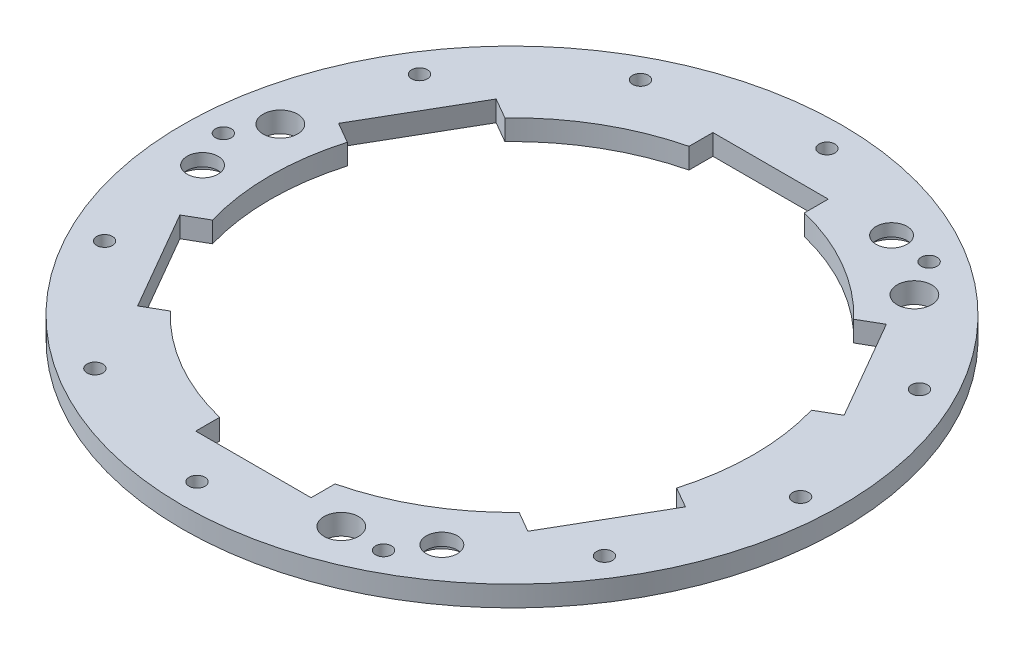
SolidWorks part; units mm, degrees
material "6061 Alloy"
ref_plane "Front Plane" through (0, 0, 0) normal (0, 0, 1) x (1, 0, 0)
ref_plane "Top Plane" through (0, 0, 0) normal (0, 1, 0) x (1, 0, 0)
ref_plane "Right Plane" through (0, 0, 0) normal (1, 0, 0) x (0, 0, -1)
sketch "Sketch1" plane through (0, 0, 0) normal (0, 1, 0) x (1, 0, 0)
  line L0 (-13.335, -54.2656) -> (-13.335, -58.1814)
  line L1 (13.335, -54.2656) -> (13.335, -58.1814)
  line L2 (-13.335, -59.7901) -> (13.335, -59.7901)
  line L3 (13.335, -58.1814) -> (13.335, -59.7901)
  line L4 (-13.335, -58.1814) -> (-13.335, -59.7901)
  line L5 (0, 0) -> (-65.7887, -5.7558) construction
  line L6 (0, 0) -> (-3.0468, -69.7835) construction
  line L7 (0, 0) -> (0, -26.4169) construction
  line L9 (-65.0367, 11.4677) -> (0, 0) construction
  circle A0 centre (0, 0) radius 55.88
  circle A1 centre (0, 0) radius 76.2
  circle A2 centre (0, 0) radius 59.69
  circle A3 centre (-3.0468, -69.7835) radius 1.8288
  circle A4 centre (-65.7887, -5.7558) radius 3.589
  circle A5 centre (-65.0367, 11.4677) radius 3.9903
  point P24 (0, 0)
  point P29 (0, 0)
  dimension "D1" = 111.76
  dimension "D2" = 152.4
  dimension "D8" = 3.6576
  dimension "D11" = 7.178
  dimension "D12" = 7.9807
  dimension "D4" = 13.335
  dimension "D5" = 13.335
  dimension "D7" = 69.85
  dimension "D6" = 5.5245
  dimension "D9" = 66.04
  dimension "D10" = 82.5
  dimension "D15" = 15
  dimension "D13" = 2.5
  dimension "D3" = 3.81
extrude "Boss-Extrude1" add sketch "Sketch1" along normal blind 4.7625 contours L1 A2 L0 A0 | A1 A2 A0 region at (-15.0127, 0, 56.2235) region at (-74.0447, 0, 0)
pattern_circular "CirPattern1" count 6 over 360 about axis through (0, 4.7625, 0) along (0, 1, 0) of face at (-13.335, 2.3813, 57.0278) of face at (13.335, 2.3813, 57.0278) of face at (0, 2.3813, 59.7901)
pattern_circular "CirPattern7" count 12 over 360 about axis through (0, 4.7625, 0) along (0, 1, 0) of face at (-3.0468, 4.7625, 71.6123)
sketch "Sketch4" plane through (0, 0, 0) normal (0, -1, 0) x (1, 0, 0)
  line L0 (0, 0) -> (-65.7887, 5.7558) construction
  line L1 (0, 0) -> (0, -39.7137) construction
  circle A0 centre (-65.7887, 5.7558) radius 5.588
  circle A2 centre (-65.7887, 5.7558) radius 3.589 construction
  circle A3 centre (-65.7887, 5.7558) radius 3.589
  point P12 (0, 0)
  dimension "D2" = 11.176
extrude "Cut-Extrude1" cut sketch "Sketch4" against normal blind 1.905 contours A0 region at (-71.2186, 0, 5.7558)
pattern_circular "CirPattern2" count 3 over 360 about axis through (0, 0, 0) along (0, 1, 0) of face at (-65.7887, 4.7625, 9.3448) of face at (-65.7887, 1.905, 2.1667) of face at (-65.7887, 1.905, 0.1678) of face at (-65.0367, 4.7625, -7.4774)
sketch "Sketch5" plane through (0, 4.7625, 0) normal (0, 1, 0) x (1, 0, 0)
  line L0 (0, 0) -> (-20.0894, -55.1952)
  line L1 (0, 0) -> (0, -18.6852)
  line L2 (-16.5968, -53.0258) -> (-18.2257, -57.5011) construction
  line L3 (-18.2257, -57.5011) -> (-22.9993, -55.7636) construction
  line L4 (-22.9993, -55.7636) -> (-21.3704, -51.2884) construction
  line L5 (-59.7924, -7.9638) -> (-55.1022, -7.1368)
  line L6 (-54.2201, -12.1397) -> (-58.9103, -12.9667)
  line L7 (-58.9103, -12.9667) -> (-59.7924, -7.9638)
  line L8 (-36.7931, 47.7998) -> (-33.7318, 44.1515)
  line L9 (-37.6233, 40.8862) -> (-40.6846, 44.5345)
  line L10 (-40.6846, 44.5345) -> (-36.7931, 47.7998)
  line L11 (22.9993, 55.7636) -> (21.3704, 51.2884)
  line L12 (16.5968, 53.0258) -> (18.2257, 57.5011)
  line L13 (18.2257, 57.5011) -> (22.9993, 55.7636)
  line L14 (59.7924, 7.9638) -> (55.1022, 7.1368)
  line L15 (54.2201, 12.1397) -> (58.9103, 12.9667)
  line L16 (58.9103, 12.9667) -> (59.7924, 7.9638)
  line L17 (36.7931, -47.7998) -> (33.7318, -44.1515)
  line L18 (37.6233, -40.8862) -> (40.6846, -44.5345)
  line L19 (40.6846, -44.5345) -> (36.7931, -47.7998)
  circle A0 centre (0, 0) radius 55.5625
  circle A1 centre (0, 0) radius 58.7375 construction
  circle A2 centre (0, 0) radius 55.5625
  circle A3 centre (0, 0) radius 55.5625
  circle A4 centre (0, 0) radius 55.5625
  circle A5 centre (0, 0) radius 55.5625
  circle A6 centre (0, 0) radius 55.5625
  circle A7 centre (0, 0) radius 76.2
  circle A8 centre (0, 0) radius 63.5
  point P38 (0, 0)
  dimension "D1" = 111.125
  dimension "D3" = 20
  dimension "D4" = 2.54
  dimension "D5" = 4.7625
  dimension "D6" = 2.54
  dimension "D2" = 3.175
  dimension "D8" = 12.7
  dimension "D7" = 6
split line "Split Line1" [suppressed]
equation "\"Middle Coupler Inner Daimeter\"= 3.875in"
equation "\"Middle Coupler  Wall Thickness\" = 0.25in"
equation "\"Middle Coupler Bottom Thickness\"= 0.2in"
equation "\"Bearing Rail Offset\"= 0.45in"
equation "\"3-56 UNF Tap\"= 0.089in"
equation "\"3-56 UNF Clearance\"= 0.104in"
equation "\"Ball Bearing Distance\"= 0.03in"
equation "\"D1@Sketch1\"=\"Middle Coupler Inner Daimeter\"+0.5+0.0125*2in"
equation "\"TCA Outer Diameter\" = 6in"
equation "\"D2@Sketch1\"=\"TCA Outer Diameter\""
equation "\"D4@Sketch1\"=0.50 + (0.05/2)"
equation "\"D5@Sketch1\"=\"D4@Sketch1\""
equation "\"D7@Sketch1\"=(\"D2@Sketch1\"-0.5)/2"
equation "\"D8@Sketch1\"=\"6-32 Clearance\""
equation "\"Interstage Aeroframe Wall Thickness\" = 0.072in"
equation "\"Compression Spring OD\"= 0.42in"
equation "\"10-24 Tap\"= 0.157in"
equation "\"10-24 Clearance\"= 0.196in"
equation "\"D2@Sketch4\"=\"Compression Spring OD\"+0.02"
equation "\"D3@Sketch1\"=0.125in+(0.05/2)"
equation "\"Lower Stage Fuselage Wall Thickness\" = 0.25in"
equation "\"6-32 Tap\" = 0.107in"
equation "\"1/4-20 Tap\" = 0.201in"
equation "\"3-48 Tap\"= 0.079in"
equation "\"12-24 Tap\" = 0.177in"
equation "\"3-48 Clearance\" = 0.104in"
equation "\"6-32 Clearance\" = 0.144"
equation "\"D6@Sketch1\"=3/16 + 0.03"
equation "\"D9@Sketch1\"=(\"D2@Sketch1\"+\"D1@Sketch1\")/4+0.1-.1"
equation "\"D1@Sketch5\"=\"Middle Coupler Inner Daimeter\"+0.5"
equation "\"D5@Sketch5\"=3/16"
equation "\"D6@Sketch5\"=\"D4@Sketch5\""
equation "\"D1@Boss-Extrude1\"=3/16"
